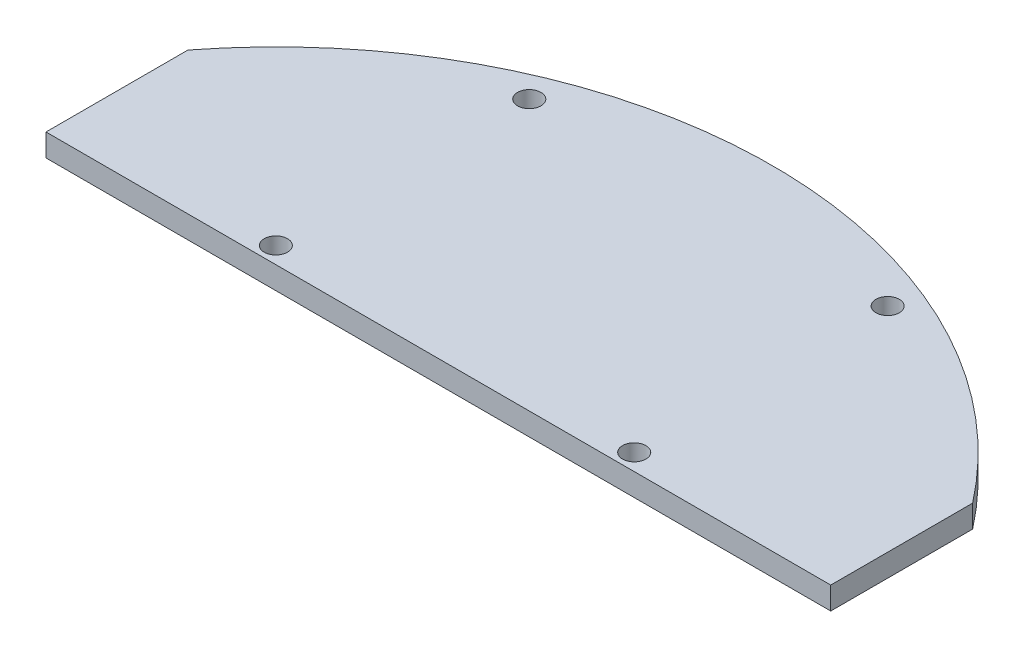
SolidWorks part; units mm, degrees
ref_plane "Front Plane" through (0, 0, 0) normal (0, 0, 1) x (1, 0, 0)
ref_plane "Top Plane" through (0, 0, 0) normal (0, 1, 0) x (1, 0, 0)
ref_plane "Right Plane" through (0, 0, 0) normal (1, 0, 0) x (0, 0, -1)
sketch "Sketch1" plane through (0, 0, 0) normal (0, 1, 0) x (1, 0, 0)
  line L3 (0, 0) -> (49.4975, 49.4975) construction
  line L4 (0, 0) -> (26.7878, 64.6716) construction
  line L5 (25.2571, 60.976) -> (25.2571, 25.2571) construction
  line L14 (-25.2571, 60.976) -> (-25.2571, 25.2571) construction
  line L15 (0, 0) -> (-26.7878, 64.6716) construction
  line L16 (0, 0) -> (-49.4975, 49.4975) construction
  line L18 (-55.3067, 42.9088) -> (-55.3067, 22.9088)
  line L19 (55.3067, 42.9088) -> (55.3067, 22.9088)
  line L20 (-55.3067, 22.9088) -> (55.3067, 22.9088)
  circle A1 centre (25.2571, 60.976) radius 1.65
  circle A3 centre (25.2571, 25.2571) radius 1.65
  circle A10 centre (-25.2571, 25.2571) radius 1.65
  circle A12 centre (-25.2571, 60.976) radius 1.65
  arc A14 (55.3067, 42.9088) -> (-55.3067, 42.9088) centre (0, 0) ccw
  dimension "D5" = 3.3
  dimension "D9" = 20
  dimension "D4" = 22.5
  dimension "D6" = 4
  dimension "D8" = 35.7189
extrude "Boss-Extrude2" add sketch "Sketch1" along normal blind 3.175
